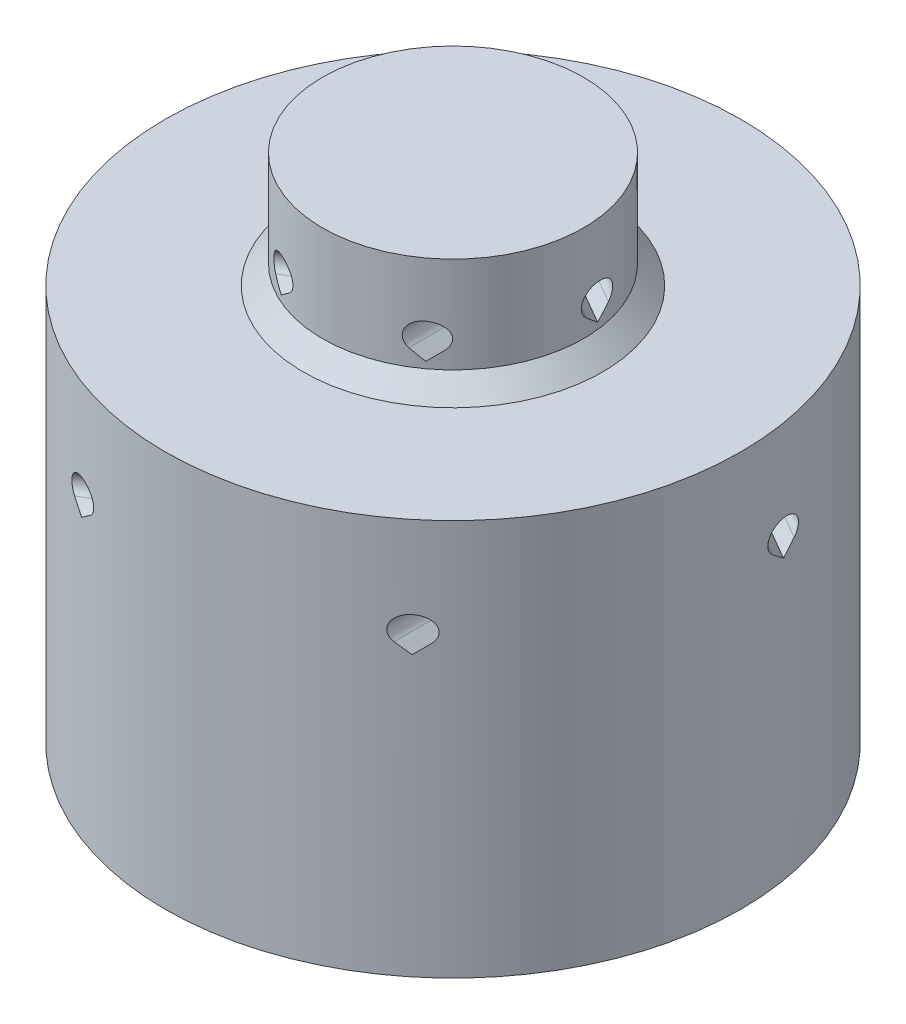
SolidWorks part; units mm, degrees
material "ASTM A36 Steel"
ref_plane "Front Plane" through (0, 0, 0) normal (0, 0, 1) x (1, 0, 0)
ref_plane "Top Plane" through (0, 0, 0) normal (0, 1, 0) x (1, 0, 0)
ref_plane "Right Plane" through (0, 0, 0) normal (1, 0, 0) x (0, 0, -1)
ref_axis "Axis1" through (0, 42.935, 0) along (0, -1, 0)
sketch "Sketch1" plane through (0, 0, 0) normal (0, 0, 1) x (1, 0, 0)
  line L1 (-5.3975, 0) -> (-5.3975, -3.9688)
  line L2 (-6.1912, -4.7625) -> (-11.9062, -4.7625)
  line L3 (-11.9062, -4.7625) -> (-11.9062, -7.1755)
  line L7 (-3.81, -1.5875) -> (-3.81, -13.0175)
  line L8 (-3.81, -13.0175) -> (-2.54, -14.2875)
  line L9 (-2.54, -14.2875) -> (-2.54, -16.8275)
  line L10 (-2.54, -16.8275) -> (-3.3337, -16.8275)
  line L11 (-3.3337, -16.8275) -> (-3.3337, -14.6163)
  line L12 (-3.3337, -14.6163) -> (-4.6037, -13.3463)
  line L13 (-4.6037, -13.3463) -> (-4.6037, -7.9375)
  line L14 (0, -1.5875) -> (0, -17.8202) construction
  line L15 (-4.6037, -7.9375) -> (-8.128, -7.9375)
  line L16 (-8.128, -7.9375) -> (-8.128, -7.1755)
  line L17 (-8.128, -7.1755) -> (-11.9062, -7.1755)
  line L19 (-5.3975, 0) -> (-4.445, 0)
  line L20 (-4.445, 0) -> (-4.445, -1.5875)
  line L21 (-4.445, -1.5875) -> (-3.81, -1.5875)
  line L22 (-6.1912, -4.7625) -> (-5.3975, -3.9688)
  point P10 (-8.128, -7.5565)
  dimension "D1" = 3.81
  dimension "D2" = 2.54
  dimension "D3" = 135
  dimension "D4" = 11.43
  dimension "D5" = 2.54
  dimension "D6" = 1.5875
  dimension "D7" = 3.175
  dimension "D8" = 0.7937
  dimension "D9" = 0.7937
  dimension "D10" = 0.762
  dimension "D11" = 1.5875
  dimension "D12" = 11.9062
  dimension "D13" = 3.175
  dimension "D14" = 135
  dimension "D15" = 8.128
  dimension "D16" = 4.445
  dimension "D17" = 0.7937
  dimension "D18" = 0.7937
revolve "Revolve1" add sketch "Sketch1" angle 360 about L14
sketch "Sketch2" plane through (0, 0, 0) normal (0, 0, 1) x (1, 0, 0)
  line L0 (-8.128, -7.9375) -> (-8.128, -14.2875)
  line L1 (-8.128, -7.1755) -> (-11.9062, -7.1755) construction
  line L2 (-8.128, -14.2875) -> (-4.445, -17.9705)
  line L3 (-4.445, -17.9705) -> (-4.445, -24.3205)
  line L4 (-4.445, -24.3205) -> (-6.35, -24.3205)
  line L5 (-6.35, -24.3205) -> (-6.35, -21.1455)
  line L7 (-11.9062, -7.1755) -> (-11.9062, -21.1455)
  line L8 (-10.3886, -21.1455) -> (-11.9062, -21.1455)
  line L9 (0, 42.935) -> (0, -67.065) construction
  line L10 (-8.128, -7.9375) -> (-8.128, -7.1755)
  line L11 (-8.128, -7.1755) -> (-11.9062, -7.1755)
  line L13 (0, -1.5875) -> (0, -17.8202) construction
  line L14 (-6.35, -21.1455) -> (-7.3152, -21.1455)
  line L15 (-7.3152, -21.1455) -> (-7.3152, -19.1643)
  line L16 (-7.3152, -19.1643) -> (-10.3886, -19.1643)
  line L17 (-10.3886, -19.1643) -> (-10.3886, -21.1455)
  point P2 (-11.8448, -7.1755)
  point P18 (-11.9062, -7.1755)
  dimension "D1" = 4.445
  dimension "D2" = 3.175
  dimension "D3" = 135
  dimension "D4" = 6.35
  dimension "D5" = 6.35
  dimension "D6" = 6.35
  dimension "D7" = 3.0734
  dimension "D8" = 1.9812
  dimension "D9" = 10.3886
revolve "Revolve2" add sketch "Sketch2" angle 360 about L14
sketch "Sketch3" plane through (0, 0, 0) normal (0, 0, 1) x (1, 0, 0)
  line L0 (-4.445, -1.5875) -> (0, -1.5875)
  line L1 (4.445, -1.5875) -> (-4.445, -1.5875) construction
  line L2 (0, -1.5875) -> (0, 0)
  line L3 (0, 0) -> (-4.445, 0)
  line L4 (-4.445, 0) -> (-4.445, -1.5875)
revolve "Revolve3" add sketch "Sketch3" angle 360 about L2
sketch "Sketch8" plane through (0, 0, 0) normal (0, 0, 1) x (1, 0, 0)
  line L0 (-3.2147, -3.6994) -> (-3.6356, -3.2784)
  line L1 (-2.7937, -3.2784) -> (-3.2147, -3.6994)
  line L2 (-3.2147, -2.8575) -> (-3.2147, -3.6994) construction
  line L3 (-3.81, -1.5875) -> (-3.81, -13.0175) construction
  line L4 (5.3975, 0) -> (-5.3975, 0) construction
  arc A0 (-3.6356, -3.2784) -> (-2.7937, -3.2784) centre (-3.2147, -2.8575) cw
  point P4 (-3.5416, -4.5666)
  point P5 (-3.81, -2.8575)
  point P6 (0, 0)
  point P7 (0, 0)
  dimension "D2" = 0.5953
  dimension "D1" = 90
  dimension "D3" = 2.8575
extrude "Cut-Extrude1" cut sketch "Sketch8" against normal through all
pattern_circular "CirPattern1" count 6 over 360 about axis through (0, 42.935, 0) along (0, -1, 0) of "Cut-Extrude1"
sketch "Sketch9" plane through (0, 0, 0) normal (0, 0, 1) x (1, 0, 0)
  line L0 (-7.5327, -9.6049) -> (-7.9536, -9.1839)
  line L1 (-7.1117, -9.1839) -> (-7.5327, -9.6049)
  line L2 (-7.5327, -9.6049) -> (-7.5327, -8.763) construction
  line L3 (-8.128, -7.9375) -> (-8.128, -14.2875) construction
  line L5 (-8.128, -7.1755) -> (-11.9062, -7.1755) construction
  arc A0 (-7.9536, -9.1839) -> (-7.1117, -9.1839) centre (-7.5327, -8.763) cw
  point P4 (-8.128, -8.763)
  point P5 (0, 0)
  dimension "D2" = 0.5953
  dimension "D1" = 90
  dimension "D3" = 1.5875
extrude "Cut-Extrude2" cut sketch "Sketch9" against normal through all
pattern_circular "CirPattern2" count 6 over 360 about axis through (0, 42.935, 0) along (0, -1, 0) of "Cut-Extrude2"
ref_axis "Axis2" through (13.0969, 0, 0) along (-1, 0, 0)
ref_axis "Axis3" through (0, 0, -13.0969) along (0, 0, 1)
equation "\".o625\"=0.0585896"
